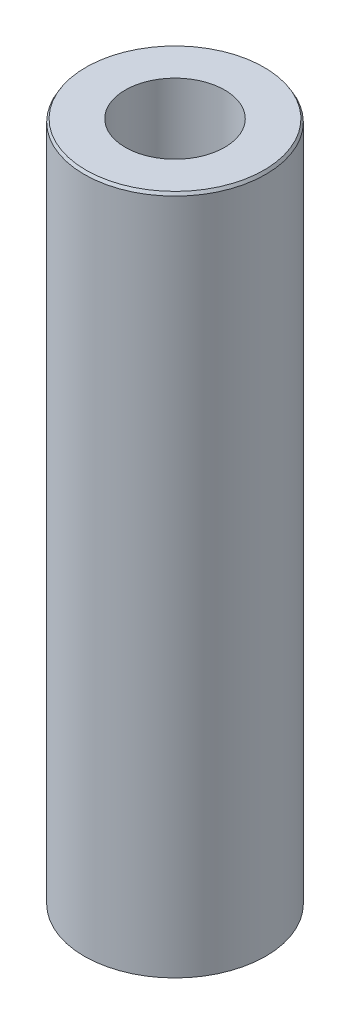
SolidWorks part; units mm, degrees
ref_plane "Front Plane" through (0, 0, 0) normal (0, 0, 1) x (1, 0, 0)
ref_plane "Top Plane" through (0, 0, 0) normal (0, 1, 0) x (1, 0, 0)
ref_plane "Right Plane" through (0, 0, 0) normal (1, 0, 0) x (0, 0, -1)
sketch "Sketch1" plane through (0, 0, 0) normal (0, 1, 0) x (1, 0, 0)
  circle A0 centre (0, 0) radius 57.5
  dimension "SHAFT_OD" = 115
extrude "Boss-Extrude1" add sketch "Sketch1" along normal blind 431.863
sketch "Sketch2" plane through (0, 0, 0) normal (0, 1, 0) x (1, 0, 0)
  circle A0 centre (0, 0) radius 31.4999
  dimension "BORE_D" = 62.9998
extrude "Cut-Extrude1" cut sketch "Sketch2" along normal through all
chamfer "Chamfer1" distance 1.8431 angle 30 2 edges at (0, 431.863, 57.5) (0, 0, 57.5) first distance on face at (0, 431.863, 57.5) first distance on face at (0, 0, 31.4999)
